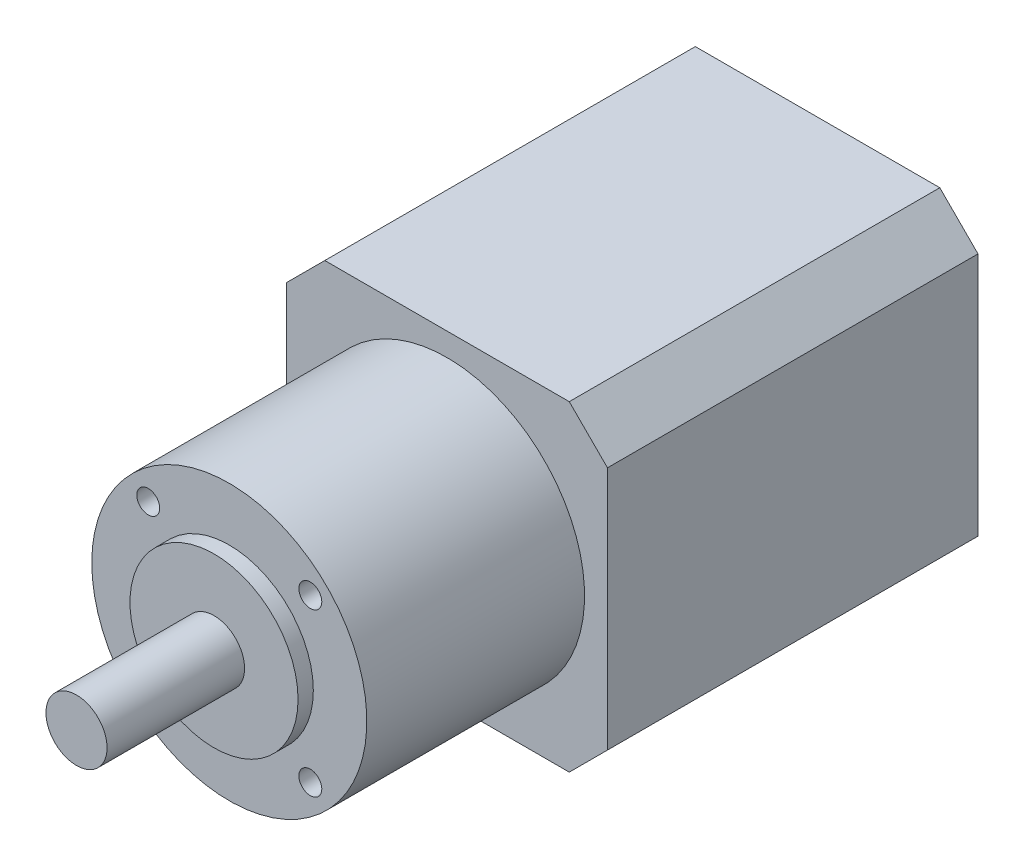
SolidWorks part; units mm, degrees
ref_plane "Front Plane" through (0, 0, 0) normal (0, 0, 1) x (1, 0, 0)
ref_plane "Top Plane" through (0, 0, 0) normal (0, 1, 0) x (1, 0, 0)
ref_plane "Right Plane" through (0, 0, 0) normal (1, 0, 0) x (0, 0, -1)
sketch "Sketch1" plane through (0, 0, 0) normal (0, 0, 1) x (1, 0, 0)
  line L1 (-21, 21) -> (21, 21)
  line L2 (-21, 21) -> (-21, -21)
  line L3 (-21, -21) -> (21, -21)
  line L4 (21, 21) -> (21, -21)
  line L5 (-21, 21) -> (21, -21) construction
  line L6 (-21, -21) -> (21, 21) construction
  point P0 (0, 0)
  dimension "D1" = 42
  dimension "D2" = 42
extrude "Boss-Extrude1" add sketch "Sketch1" along normal blind 48.5
sketch "Sketch2" plane through (0, 0, 48.5) normal (0, 0, 1) x (1, 0, 0)
  circle A0 centre (0, 0) radius 18
  dimension "D1" = 36
extrude "Boss-Extrude2" add sketch "Sketch2" along normal blind 28.5
sketch "Sketch3" plane through (0, 0, 77) normal (0, 0, 1) x (1, 0, 0)
  circle A0 centre (0, 0) radius 11
  circle A1 centre (0, 0) radius 4
  dimension "D1" = 22
  dimension "D2" = 8
extrude "Boss-Extrude3" add sketch "Sketch3" along normal blind 2
extrude "Boss-Extrude4" add sketch "Sketch3<2>" along normal blind 20 contours A1
sketch "Sketch3<2>" plane through (0, 0, 77) normal (0, 0, 1) x (1, 0, 0) same geometry as "Sketch3"
sketch "Sketch4" plane through (0, 0, 77) normal (0, 0, 1) x (1, 0, 0)
  line L1 (-10.6066, 10.6066) -> (10.6066, 10.6066)
  line L2 (-10.6066, 10.6066) -> (-10.6066, -10.6066)
  line L3 (-10.6066, -10.6066) -> (10.6066, -10.6066)
  line L4 (10.6066, 10.6066) -> (10.6066, -10.6066)
  line L5 (-10.6066, 10.6066) -> (10.6066, -10.6066) construction
  line L6 (-10.6066, -10.6066) -> (10.6066, 10.6066) construction
  circle A0 centre (0, 0) radius 15
  circle A1 centre (10.6066, -10.6066) radius 1.5
  circle A2 centre (-10.6066, -10.6066) radius 1.5
  circle A3 centre (-10.6066, 10.6066) radius 1.5
  circle A4 centre (10.6066, 10.6066) radius 1.5
  point P17 (0, 0)
  dimension "D1" = 30
  dimension "D2" = 3
  dimension "D3" = 4
extrude "Cut-Extrude1" cut sketch "Sketch4" against normal blind 10 contours A2 | A3 | A4 | A1
chamfer "Chamfer1" distance 5 angle 45 4 edges at (21, -21, 24.25) (21, 21, 24.25) (-21, 21, 24.25) (-21, -21, 24.25)
